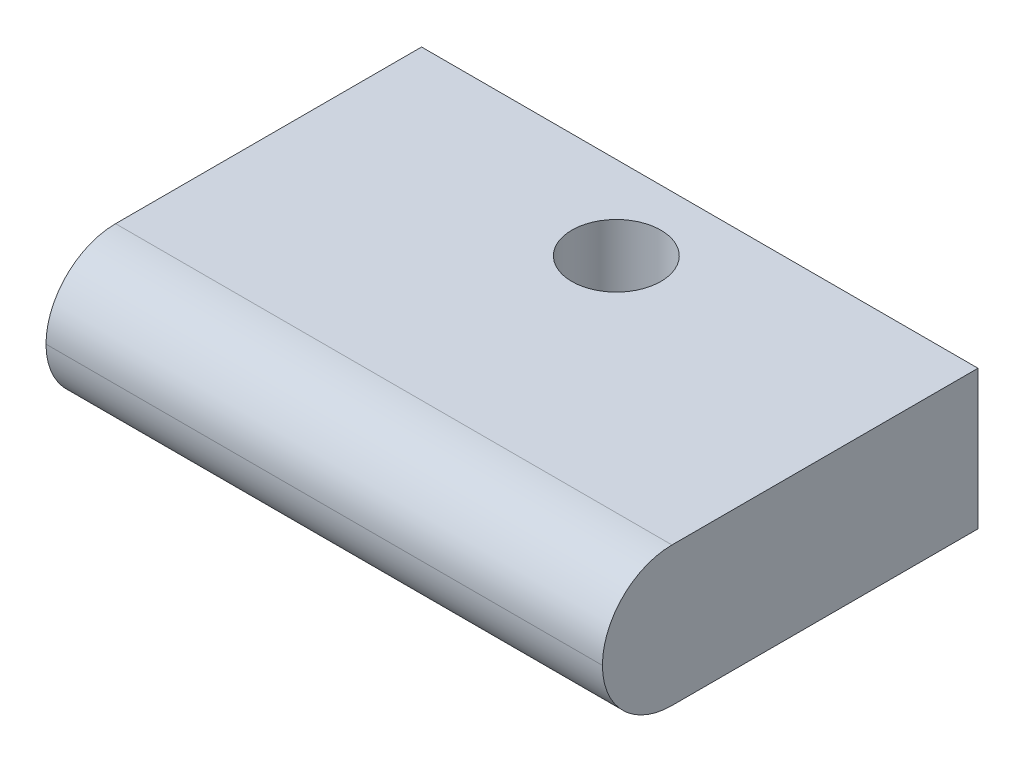
SolidWorks part; units mm, degrees
ref_plane "Front Plane" through (0, 0, 0) normal (0, 0, 1) x (1, 0, 0)
ref_plane "Top Plane" through (0, 0, 0) normal (0, 1, 0) x (1, 0, 0)
ref_plane "Right Plane" through (0, 0, 0) normal (1, 0, 0) x (0, 0, -1)
sketch "Sketch1" plane through (0, 0, 0) normal (0, 1, 0) x (1, 0, 0)
  line L2 (-10, 6.75) -> (-10, -6.75)
  line L3 (-10, -6.75) -> (10, -6.75)
  line L4 (10, 6.75) -> (10, -6.75)
  line L7 (10, 6.75) -> (-10, 6.75)
  point P3 (10, 0)
  point P4 (0, -6.75)
  dimension "D1" = 13.5
  dimension "D2" = 20
extrude "Boss-Extrude1" add sketch "Sketch1" along normal blind 5
sketch "Sketch2" plane through (0, 5, 0) normal (0, 1, 0) x (1, 0, 0)
  line L0 (0, 3.5) -> (0, 0.6972) construction
  line L3 (10, 6.75) -> (-10, 6.75) construction
  point P0 (0, 3.75)
  point P10 (0, 0)
  point P11 (0, 3.0375)
  point P12 (0, 0)
  point P13 (0.4194, 1.6972)
  point P14 (-0.2006, 2.4996)
  dimension "D1" = 3
hole_wizard "Ø3.2 (3.2) M2 heat set" positions "Sketch2" profile "Sketch3" hole size "Ø3.2" standard "ANSI Metric" end condition up to next
sketch "Sketch3" plane through (0, 5, -3.75) normal (1, 0, 0) x (0, 0, 1)
  line L0 (0, 0) -> (0, 5)
  line L1 (0, 5) -> (1.6, 5)
  line L2 (1.6, 5) -> (1.6, 0)
  line L5 (1.6, 0) -> (0, 0)
  line L11 (0, -6.35) -> (0, 107.95) construction
  dimension "Thru Hole Dia." = 3.2
  dimension "Thru Hole Depth" = 5
fillet "Fillet2" radius 2.5 2 edges at (0, 0, 6.75) (0, 5, 6.75)
